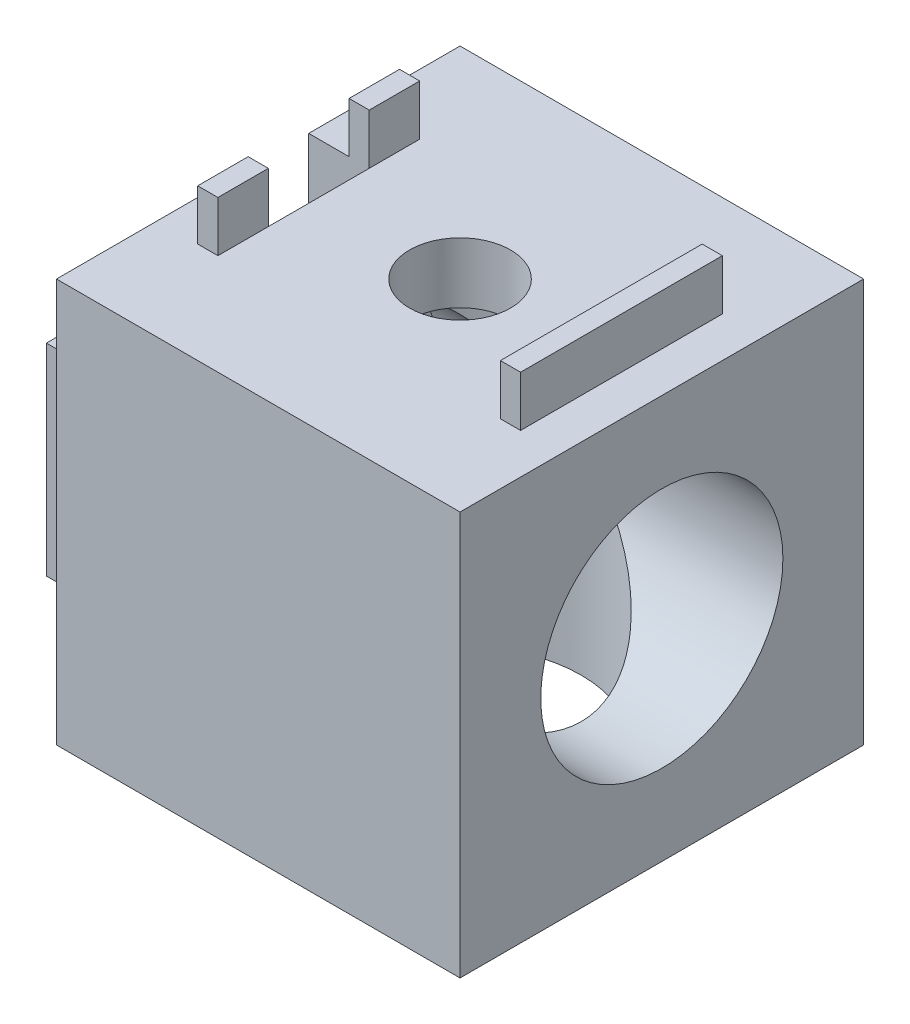
SolidWorks part; units mm, degrees
ref_plane "Front Plane" through (0, 0, 0) normal (0, 0, 1) x (1, 0, 0)
ref_plane "Top Plane" through (0, 0, 0) normal (0, 1, 0) x (1, 0, 0)
ref_plane "Right Plane" through (0, 0, 0) normal (1, 0, 0) x (0, 0, -1)
sketch "Sketch1" plane through (0, 0, 0) normal (0, 1, 0) x (1, 0, 0)
  line L0 (0, 7.5) -> (3, 7.5)
  line L1 (0, 0) -> (20, 0)
  line L2 (0, 0) -> (0, 7.5)
  line L3 (0, 20) -> (20, 20)
  line L4 (20, 0) -> (20, 20)
  line L5 (3, 7.5) -> (3, 12.5)
  line L6 (3, 12.5) -> (0, 12.5)
  line L7 (0, 12.5) -> (0, 20)
extrude "Boss-Extrude1" add sketch "Sketch1" along normal blind 20
sketch "Sketch2" plane through (0, 20, 0) normal (0, 1, 0) x (1, 0, 0)
  line L1 (2, 7.5) -> (3, 7.5)
  line L2 (2, 7.5) -> (2, 5)
  line L3 (2, 5) -> (3, 5)
  line L4 (3, 7.5) -> (3, 5)
  line L5 (2, 15) -> (3, 15)
  line L6 (2, 15) -> (2, 12.5)
  line L7 (2, 12.5) -> (3, 12.5)
  line L8 (3, 15) -> (3, 12.5)
  line L9 (17, 15) -> (18, 15)
  line L10 (17, 15) -> (17, 5)
  line L11 (17, 5) -> (18, 5)
  line L12 (18, 15) -> (18, 5)
  circle A0 centre (10, 10) radius 2.5
extrude "Boss-Extrude2" add sketch "Sketch2" along normal blind 2.5 contours L4 L2 L3 | L8 L5 L6 A0 | L12 L9 L10 L11 region at (2.5, 20, -6.25) region at (2.5, 20, -13.75) region at (17.5, 20, -10)
extrude "Cut-Extrude1" cut sketch "Sketch2<3>" against normal through all contours A0 region at (10, 20, -10)
sketch "Sketch2<3>" plane through (0, 20, 0) normal (0, 1, 0) x (1, 0, 0) same geometry as "Sketch2"
sketch "Sketch3" plane through (0, 0, 0) normal (-1, 0, 0) x (0, 0, 1)
  line L1 (-2, 15) -> (-3, 15)
  line L2 (-2, 15) -> (-2, 5)
  line L3 (-2, 5) -> (-3, 5)
  line L4 (-3, 15) -> (-3, 5)
  line L5 (-18, 15) -> (-17, 15)
  line L6 (-18, 15) -> (-18, 5)
  line L7 (-18, 5) -> (-17, 5)
  line L8 (-17, 15) -> (-17, 5)
extrude "Boss-Extrude3" add sketch "Sketch3" along normal blind 2.5
sketch "Sketch4" plane through (0, 0, -20) normal (0, 0, -1) x (-1, 0, 0)
  line L1 (-18, 15) -> (-17, 15)
  line L2 (-18, 15) -> (-18, 5)
  line L3 (-18, 5) -> (-17, 5)
  line L4 (-17, 15) -> (-17, 5)
  line L5 (-2, 15) -> (-3, 15)
  line L6 (-2, 15) -> (-2, 5)
  line L7 (-2, 5) -> (-3, 5)
  line L8 (-3, 15) -> (-3, 5)
  line L9 (-15, 3) -> (-5, 3)
  line L10 (-15, 3) -> (-15, 2)
  line L11 (-15, 2) -> (-5, 2)
  line L12 (-5, 3) -> (-5, 2)
  circle A0 centre (-10, 10) radius 2.5
sketch "Sketch5" plane through (20, 0, 0) normal (1, 0, 0) x (0, 0, -1)
  circle A0 centre (10, 10) radius 6
extrude "Cut-Extrude3" cut sketch "Sketch5" against normal blind 17
sketch "Sketch7" plane through (0, 0, 0) normal (0, -1, 0) x (1, 0, 0)
  circle A0 centre (10, -10) radius 6
extrude "Cut-Extrude5" cut sketch "Sketch7" against normal blind 17
